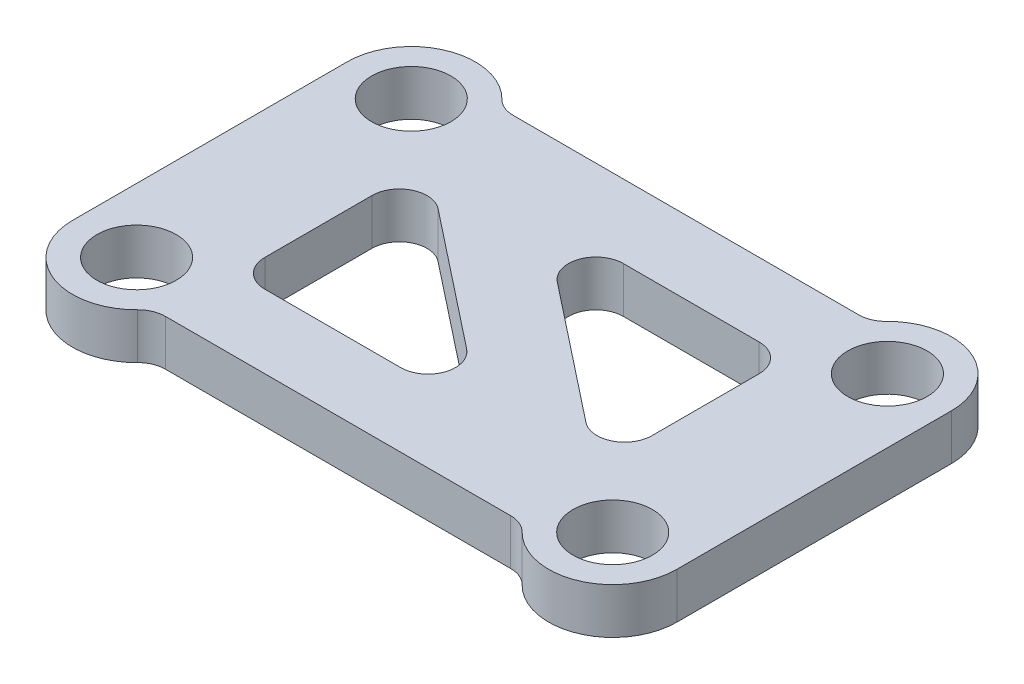
SolidWorks part; units mm, degrees
material "6061-T6 (SS)"
ref_plane "Front Plane" through (0, 0, 0) normal (0, 0, 1) x (1, 0, 0)
ref_plane "Top Plane" through (0, 0, 0) normal (0, 1, 0) x (1, 0, 0)
ref_plane "Right Plane" through (0, 0, 0) normal (1, 0, 0) x (0, 0, -1)
sketch "Sketch1" plane through (0, -19.05, 0) normal (0, -1, 0) x (1, 0, 0)
  line L0 (-29.21, 9.525) -> (-29.21, -9.525) construction
  line L5 (-24.765, 9.525) -> (-24.765, -9.525)
  line L6 (-33.655, 9.525) -> (-33.655, -9.525)
  line L7 (3.81, 9.525) -> (3.81, -9.525) construction
  line L8 (8.255, 9.525) -> (8.255, -9.525)
  line L9 (-0.635, 9.525) -> (-0.635, -9.525)
  arc A4 (-24.765, 9.525) -> (-33.655, 9.525) centre (-29.21, 9.525) ccw
  arc A5 (-33.655, -9.525) -> (-24.765, -9.525) centre (-29.21, -9.525) ccw
  arc A6 (8.255, 9.525) -> (-0.635, 9.525) centre (3.81, 9.525) ccw
  arc A7 (-0.635, -9.525) -> (8.255, -9.525) centre (3.81, -9.525) ccw
  point P2 (-29.21, 0)
  point P12 (3.81, 0)
  dimension "D1" = 4.445
  dimension "D2" = 4.445
extrude "Boss-Extrude2" add sketch "Sketch1" along normal blind 3.175
sketch "Sketch7" plane through (0, -22.225, 0) normal (0, -1, 0) x (1, 0, 0)
  line L0 (-29.21, 9.525) -> (-0.635, 9.525)
  line L1 (-0.635, 9.525) -> (-24.765, -9.525)
  line L2 (-24.765, -9.525) -> (3.81, -9.525)
  point P8 (-24.765, -9.525)
  point P9 (-0.635, 9.525)
extrude "Extrude-Thin1" add sketch "Sketch7" against normal up to surface (3.175 mm away) thin up to face at (-29.21, -19.05, 0) thin type mid plane wall 5.08
hole_wizard "M5 Clearance Hole1" positions "3DSketch1" profile "Sketch5" hole size "M5" standard "ANSI Metric" end condition through all
sketch3d "3DSketch1"
  line L0 (-29.21, -22.225, 9.525) -> (-29.21, -19.05, 9.525) construction
  line L1 (-29.21, -22.225, -9.525) -> (-29.21, -19.05, -9.525) construction
  line L2 (3.81, -22.225, 9.525) -> (3.81, -19.05, 9.525) construction
  line L3 (3.81, -22.225, -9.525) -> (3.81, -19.05, -9.525) construction
  point P0 (-29.21, -22.225, 9.525)
  point P4 (-29.21, -22.225, -9.525)
  point P8 (3.81, -22.225, 9.525)
  point P12 (3.81, -22.225, -9.525)
sketch "Sketch5" plane through (-29.21, -22.225, 9.525) normal (1, 0, 0) x (0, 0, -1)
  line L0 (0, 0) -> (0, 3.175)
  line L1 (0, 3.175) -> (2.75, 3.175)
  line L2 (2.75, 3.175) -> (2.75, 0)
  line L5 (2.75, 0) -> (0, 0)
  line L11 (0, -6.35) -> (0, 107.95) construction
  dimension "Thru Hole Dia." = 5.5
  dimension "Thru Hole Depth" = 3.175
fillet "Fillet1" radius 1.905 10 edges at (-25.5622, -20.6375, -12.065) (0.1622, -20.6375, -12.065) (-17.4485, -20.6375, -6.985) (-0.635, -20.6375, -6.985) (-0.635, -20.6375, 6.2888) (-7.9515, -20.6375, 6.985) (-24.765, -20.6375, 6.985) (-24.765, -20.6375, -6.2888) (0.1622, -20.6375, 12.065) (-25.5622, -20.6375, 12.065)
